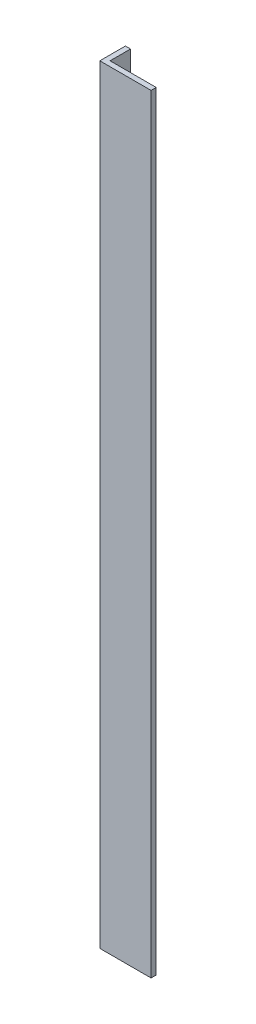
SolidWorks part; units mm, degrees
ref_plane "Front Plane" through (0, 0, 0) normal (0, 0, 1) x (1, 0, 0)
ref_plane "Top Plane" through (0, 0, 0) normal (0, 1, 0) x (1, 0, 0)
ref_plane "Right Plane" through (0, 0, 0) normal (1, 0, 0) x (0, 0, -1)
sketch "Sketch1" plane through (0, 0, 0) normal (0, 1, 0) x (1, 0, 0)
  line L0 (0, 0) -> (0, 10)
  line L1 (0, 10) -> (2, 10)
  line L2 (2, 10) -> (2, 2)
  line L3 (2, 2) -> (20, 2)
  line L4 (20, 2) -> (20, 0)
  line L5 (20, 0) -> (0, 0)
extrude "Boss-Extrude1" add sketch "Sketch1" along normal blind 300
hole_wizard "Ø3.0mm Dowel Hole1" positions "Sketch3" profile "Sketch5" hole size "Ø3.0" standard "ISO" end condition up to next
sketch "Sketch3" plane through (0, 0, 0) normal (-1, 0, 0) x (0, 0, 1)
  point P0 (-7.25, 2.75)
  point P3 (-7.25, 2.75)
sketch "Sketch5" plane through (0, 2.75, -7.25) normal (0, 1, 0) x (0, 0, 1)
  line L0 (0, 0) -> (0, 2)
  line L1 (0, 2) -> (1.5, 2)
  line L2 (1.5, 2) -> (1.5, 0)
  line L5 (1.5, 0) -> (0, 0)
  line L11 (0, -6.35) -> (0, 107.95) construction
  dimension "Thru Hole Dia." = 3
  dimension "Thru Hole Depth" = 2
hole_wizard "Ø3.0mm Dowel Hole2" positions "Sketch6" profile "Sketch7" hole size "Ø3.0" standard "ISO" end condition up to next
sketch "Sketch6" plane through (0, 0, 0) normal (-1, 0, 0) x (0, 0, 1)
  point P0 (-7.25, 211.25)
sketch "Sketch7" plane through (0, 211.25, -7.25) normal (0, 1, 0) x (0, 0, 1)
  line L0 (0, 0) -> (0, 2)
  line L1 (0, 2) -> (1.5, 2)
  line L2 (1.5, 2) -> (1.5, 0)
  line L5 (1.5, 0) -> (0, 0)
  line L11 (0, -6.35) -> (0, 107.95) construction
  dimension "Thru Hole Dia." = 3
  dimension "Thru Hole Depth" = 2
